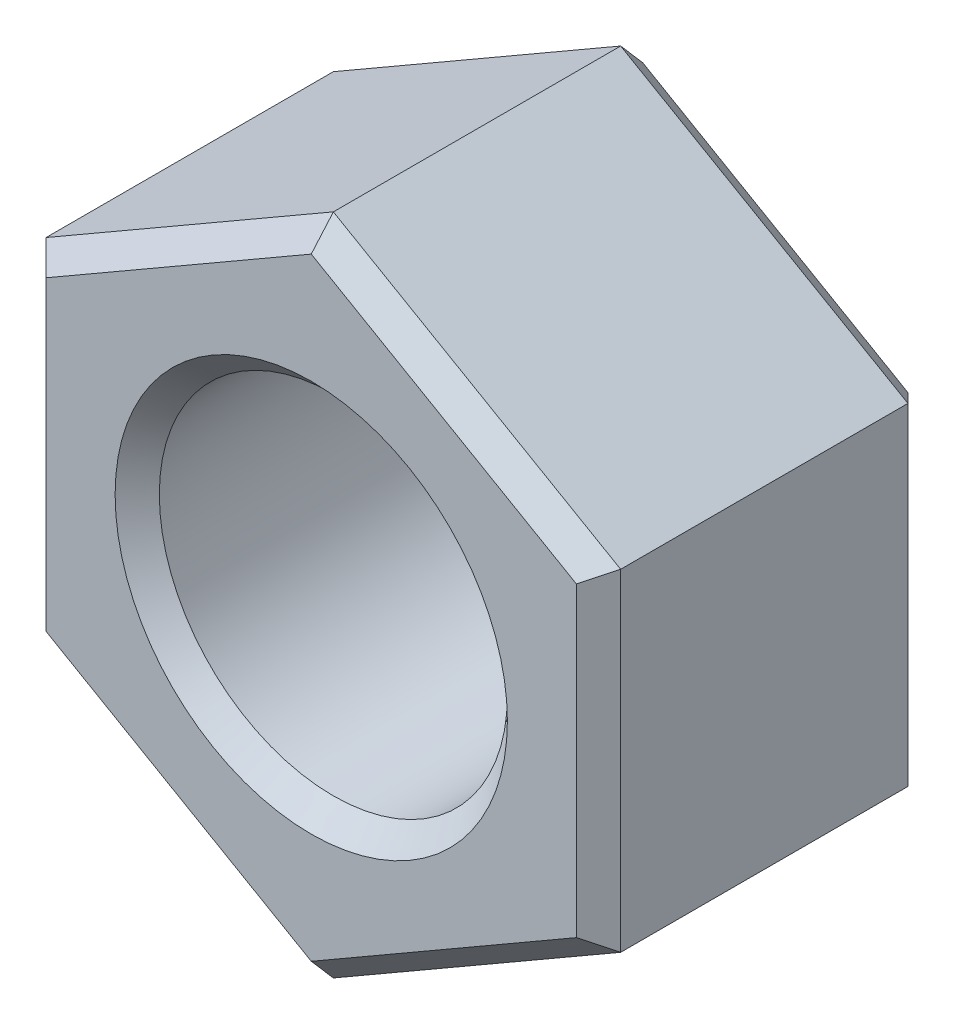
SolidWorks part; units mm, degrees
ref_plane "Front" through (0, 0, 0) normal (0, 0, 1) x (1, 0, 0)
ref_plane "Top" through (0, 0, 0) normal (0, 1, 0) x (1, 0, 0)
ref_plane "Right" through (0, 0, 0) normal (1, 0, 0) x (0, 0, -1)
sketch "Sketch1" plane through (0, 0, 0) normal (0, 0, 1) x (1, 0, 0)
  line L1 (2.6, -1.5011) -> (2.6, 1.5011)
  line L2 (2.6, 1.5011) -> (0, 3.0022)
  line L3 (0, 3.0022) -> (-2.6, 1.5011)
  line L4 (-2.6, 1.5011) -> (-2.6, -1.5011)
  line L5 (-2.6, -1.5011) -> (0, -3.0022)
  line L6 (0, -3.0022) -> (2.6, -1.5011)
  circle A0 centre (0, 0) radius 2.6 construction
  circle A1 centre (0, 0) radius 1.575
  dimension "D1" = 3.15
  dimension "D2" = 5.2
extrude "Boss-Extrude1" add sketch "Sketch1" along normal mid plane 3
chamfer "Deburs" distance 0.2 angle 45 14 edges at (1.575, 0, -1.5) (2.6, 0, -1.5) (1.3, 2.2517, -1.5) (-1.3, 2.2517, -1.5) (-2.6, 0, -1.5) (-1.3, -2.2517, -1.5) (1.3, -2.2517, -1.5) (1.575, 0, 1.5) (-1.3, -2.2517, 1.5) (-2.6, 0, 1.5) (-1.3, 2.2517, 1.5) (1.3, 2.2517, 1.5) (2.6, 0, 1.5) (1.3, -2.2517, 1.5)
equation "\"D1@Sketch1\"=\"Hardware Clearance Hole Diameter@Box Assy.Assembly\""
equation "\"D2@Sketch1\"=\"Nut Trap Diameter@Box Assy.Assembly\"-0.3mm"
